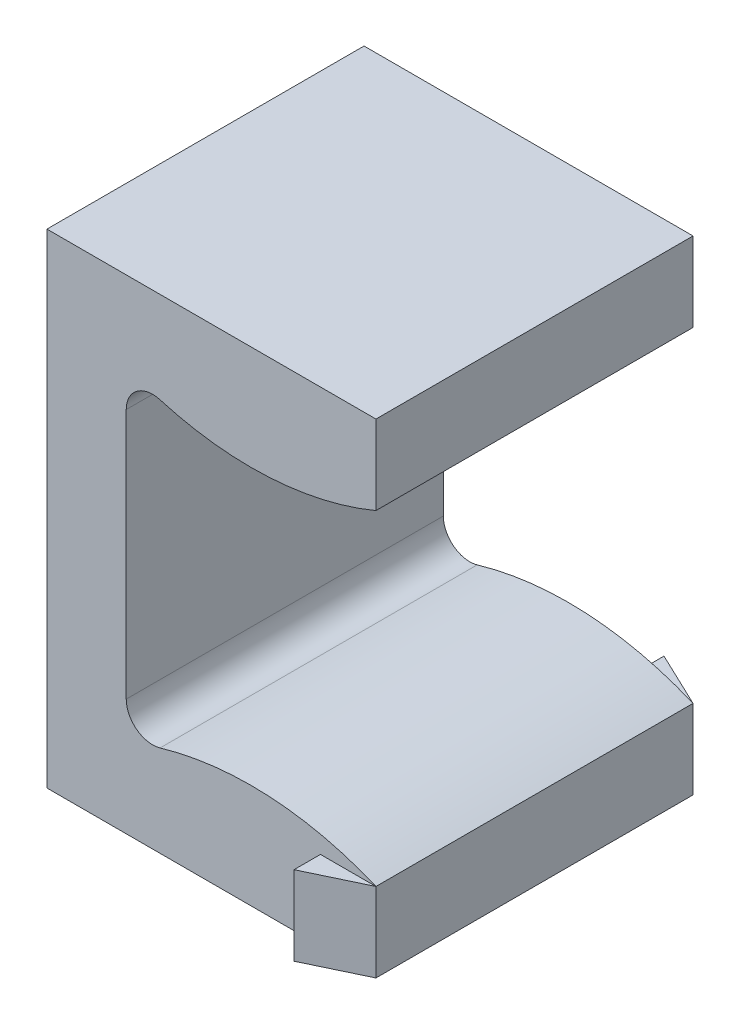
SolidWorks part; units mm, degrees
ref_plane "Front Plane" through (0, 0, 0) normal (0, 0, 1) x (1, 0, 0)
ref_plane "Top Plane" through (0, 0, 0) normal (0, 1, 0) x (1, 0, 0)
ref_plane "Right Plane" through (0, 0, 0) normal (1, 0, 0) x (0, 0, -1)
sketch "Sketch1" plane through (0, 0, 0) normal (0, 0, 1) x (1, 0, 0)
  line L2 (-159.7982, 9.1594) -> (-172.2482, 9.1594)
  line L3 (-172.2482, 9.1594) -> (-172.2482, -9.1594)
  line L7 (-169.2482, -22.8519) -> (-169.2482, 6.1594) construction
  line L13 (-142.8048, 5.1594) -> (-142.8048, -5.1594) construction
  line L23 (-159.7982, 6.1594) -> (-159.7982, 9.1594)
  line L28 (-164.5232, 5.2094) -> (-144.5007, 5.2094) construction
  line L30 (-169.2482, 6.1594) -> (-169.2482, 5.1594)
  line L34 (-169.2482, 5.1594) -> (-169.2482, -5.1594)
  line L35 (-172.2482, 0) -> (-169.2482, 0) construction
  line L36 (-169.2482, -6.1594) -> (-169.2482, -5.1594)
  line L37 (-159.7982, -6.1594) -> (-159.7982, -9.1594)
  line L38 (-159.7982, -9.1594) -> (-172.2482, -9.1594)
  arc A5 (-169.2482, 6.1594) -> (-159.7982, 6.1594) centre (-164.5232, 17.4347) ccw
  arc A6 (-169.2482, -6.1594) -> (-159.7982, -6.1594) centre (-164.5232, -17.4347) cw
  point P30 (-142.8048, 0)
  dimension "D6" = 12.2253
  dimension "D4" = 3
  dimension "D3" = 3
  dimension "D2" = 1
  dimension "D1" = 18.3188
  dimension "D5" = 12.45
extrude "MainBody" add sketch "Sketch1" along normal mid plane 12
sketch "Sketch3" plane through (0, -9.1594, 0) normal (0, -1, 0) x (1, 0, 0)
  line L0 (-159.7982, -6) -> (-161.8982, -7)
  line L1 (-161.8982, -7) -> (-161.8982, -6)
  line L2 (-172.2482, -6) -> (-159.7982, -6) construction
  line L3 (-161.8982, -6) -> (-159.7982, -6)
  line L5 (55, 0) -> (-55, 0) construction
  line L6 (-161.8982, 6) -> (-159.7982, 6)
  line L7 (-161.8982, 7) -> (-161.8982, 6)
  line L8 (-159.7982, 6) -> (-161.8982, 7)
  dimension "D1" = 2.1
  dimension "D2" = 1
extrude "Hook" add sketch "Sketch3" against normal up to vertex (3 mm away) up to point (-159.7982, -6.1594, -6)
fillet "Fillet2" radius 1 2 edges at (-169.2482, 6.1594, 0) (-169.2482, -6.1594, 0)
sketch "Sketch5" [suppressed] plane through (-172.2482, 0, 0) normal (-1, 0, 0) x (0, 0, 1)
  line L1 (-6, 9.1594) -> (6, 9.1594)
  line L2 (-6, 9.1594) -> (-6, -9.1594)
  line L3 (-6, -9.1594) -> (6, -9.1594)
  line L4 (6, 9.1594) -> (6, -9.1594)
extrude "Boss-Extrude1" [suppressed] add sketch "Sketch5" along normal blind 15
sketch "Sketch6" [suppressed] plane through (0, 9.1594, 0) normal (0, 1, 0) x (1, 0, 0)
  line L0 (-187.2482, -6) -> (-187.2482, 6) construction
  circle A0 centre (-182.2482, 0) radius 3.302
  dimension "D1" = 6.604
  dimension "D2" = 5
extrude "Cut-Extrude2" [suppressed] cut sketch "Sketch6" against normal through all
sketch "Sketch7" [suppressed] plane through (-172.2482, 0, 0) normal (-1, 0, 0) x (0, 0, 1)
  circle A0 centre (0, 0) radius 38.1
  dimension "D1" = 76.2
extrude "Boss-Extrude2" [suppressed] add sketch "Sketch7" along normal blind 5
fillet "Fillet3" [suppressed] radius 1
sketch "Sketch8" [suppressed] plane through (0, 0, 6) normal (0, 0, 1) x (1, 0, 0)
  line L6 (-172.2482, -0.635) -> (-173.4343, -0.635)
  line L8 (-172.2482, 0.635) -> (-173.4343, 0.635)
  line L10 (-172.2482, 0.635) -> (-173.4343, 0.635)
  line L11 (-172.2482, 0.635) -> (-172.2482, -0.635)
  line L12 (-159.7982, -9.1594) -> (-159.7982, -6.1594)
  line L13 (-159.7982, -9.1594) -> (-159.7982, -6.1594)
  line L14 (-169.2482, -6.1594) -> (-169.2482, 6.1594)
  line L15 (-159.7982, 6.1594) -> (-159.7982, 9.1594)
  line L16 (-159.7982, 9.1594) -> (-172.2482, 9.1594)
  line L17 (-172.2482, 9.1594) -> (-172.2482, -9.1594)
  line L18 (-172.2482, -9.1594) -> (-159.7982, -9.1594)
  line L21 (-169.2482, -6.1594) -> (-169.2482, 6.1594)
  line L22 (-159.7982, 6.1594) -> (-159.7982, 9.1594)
  line L23 (-159.7982, 9.1594) -> (-172.2482, 9.1594)
  line L24 (-172.2482, 9.1594) -> (-172.2482, -9.1594)
  line L25 (-172.2482, -9.1594) -> (-159.7982, -9.1594)
  line L26 (-172.2482, -0.635) -> (-173.4343, -0.635)
  arc A0 (-173.4343, 0.635) -> (-173.4343, -0.635) centre (-174.5342, 0) ccw
  arc A4 (-159.7982, -6.1594) -> (-169.2482, -6.1594) centre (-164.5232, -17.4347) ccw
  arc A7 (-169.2482, 6.1594) -> (-159.7982, 6.1594) centre (-164.5232, 17.4347) ccw
  arc A8 (-159.7982, -6.1594) -> (-169.2482, -6.1594) centre (-164.5232, -17.4347) ccw
  arc A11 (-169.2482, 6.1594) -> (-159.7982, 6.1594) centre (-164.5232, 17.4347) ccw
  point P6 (-172.2482, 0)
  line M14 (-172.2482, 9.1594) -> (-172.2482, -9.1594)
  dimension "D2" = 1.27
  dimension "D1" = 0
  dimension "D3" = 2.286
extrude "Slot" [suppressed] add sketch "Sketch8" against normal up to surface (12 mm away) contours L8 A0 L6 M14 up to face at (-165.6835, -0.5599, -6)
sketch "Sketch10" [suppressed] plane through (0, 0, -6) normal (0, 0, -1) x (-1, 0, 0)
  line L0 (166.0232, -9.1594) -> (172.2482, -9.1594)
  line L3 (172.2482, -9.1594) -> (166.0232, -9.1594)
  line L5 (172.2482, -9.1594) -> (187.9767, -44.4861)
  line L6 (195.4932, -61.3685) -> (192.3182, -61.3685)
  line L7 (159.7982, -6.1594) -> (159.7982, -9.1594)
  line L8 (159.7982, -6.1594) -> (159.7982, -9.1594)
  line L9 (159.7982, -9.1594) -> (172.2482, -9.1594)
  line L10 (172.2482, -9.1594) -> (172.2482, 9.1594)
  line L11 (172.2482, 9.1594) -> (159.7982, 9.1594)
  line L12 (159.7982, 9.1594) -> (159.7982, 6.1594)
  line L13 (169.2482, 6.1594) -> (169.2482, -6.1594)
  line L16 (159.7982, -9.1594) -> (172.2482, -9.1594)
  line L17 (172.2482, -9.1594) -> (172.2482, 9.1594)
  line L18 (172.2482, 9.1594) -> (159.7982, 9.1594)
  line L19 (159.7982, 9.1594) -> (159.7982, 6.1594)
  line L20 (169.2482, 6.1594) -> (169.2482, -6.1594)
  line L21 (195.4932, -61.3685) -> (201.8432, -61.3685)
  line L22 (201.8432, -61.3685) -> (201.8432, -59.781)
  line L24 (192.666, -55.0185) -> (200.9772, -55.0185)
  line L25 (169.0732, -9.1594) -> (192.3182, -61.3685)
  line L28 (201.8432, -59.781) -> (194.7864, -59.781)
  line L31 (193.3728, -56.606) -> (200.9772, -56.606)
  line L42 (200.9772, -55.0185) -> (200.9772, -56.606)
  line L43 (187.9767, -44.4861) -> (195.4932, -61.3685)
  arc A4 (169.2482, -6.1594) -> (159.7982, -6.1594) centre (164.5232, -17.4347) ccw
  arc A5 (159.7982, 6.1594) -> (169.2482, 6.1594) centre (164.5232, 17.4347) ccw
  arc A8 (169.2482, -6.1594) -> (159.7982, -6.1594) centre (164.5232, -17.4347) ccw
  arc A9 (159.7982, 6.1594) -> (169.2482, 6.1594) centre (164.5232, 17.4347) ccw
  dimension "D5" = 6.35
  dimension "D7" = 3.175
  dimension "D8" = 3.175
  dimension "D2" = 57.15
  dimension "D10" = 1.5875
  dimension "D13" = 114
  dimension "D14" = 114
  dimension "D3" = 1.5875
  dimension "D4" = 3.175
extrude "Boss-Extrude3" [suppressed] add sketch "Sketch10" against normal up to surface (12 mm away) up to face at (-165.6835, -0.5599, 6)
sketch "Sketch11" [suppressed] plane through (0, 0, -6) normal (0, 0, -1) x (-1, 0, 0)
  line L0 (159.7982, -9.1594) -> (159.7982, 9.1594)
  line L11 (169.2482, 6.1594) -> (169.2482, -6.1594)
  line L12 (159.7982, -6.1594) -> (159.7982, -9.1594)
  line L13 (159.7982, -9.1594) -> (169.0732, -9.1594)
  line L14 (169.0732, -9.1594) -> (192.3182, -61.3685)
  line L15 (192.3182, -61.3685) -> (201.8432, -61.3685)
  line L16 (201.8432, -61.3685) -> (201.8432, -59.781)
  line L17 (201.8432, -59.781) -> (194.7864, -59.781)
  line L18 (194.7864, -59.781) -> (193.3728, -56.606)
  line L19 (172.2482, -9.1594) -> (172.2482, 9.1594)
  line L20 (172.2482, 9.1594) -> (159.7982, 9.1594)
  line L21 (159.7982, 9.1594) -> (159.7982, 6.1594)
  line L22 (169.2482, 6.1594) -> (169.2482, -6.1594)
  line L23 (159.7982, -6.1594) -> (159.7982, -9.1594)
  line L24 (159.7982, -9.1594) -> (169.0732, -9.1594)
  line L25 (169.0732, -9.1594) -> (192.3182, -61.3685)
  line L26 (192.3182, -61.3685) -> (201.8432, -61.3685)
  line L27 (201.8432, -61.3685) -> (201.8432, -59.781)
  line L28 (201.8432, -59.781) -> (194.7864, -59.781)
  line L29 (194.7864, -59.781) -> (193.3728, -56.606)
  line L30 (172.2482, -9.1594) -> (172.2482, 9.1594)
  line L31 (172.2482, 9.1594) -> (159.7982, 9.1594)
  line L32 (159.7982, 9.1594) -> (159.7982, 6.1594)
  line L37 (193.3728, -56.606) -> (200.9772, -56.606)
  line L38 (193.3728, -56.606) -> (200.9772, -56.606)
  line L39 (200.9772, -56.606) -> (200.9772, -55.0185)
  line L40 (200.9772, -56.606) -> (200.9772, -55.0185)
  line L41 (192.666, -55.0185) -> (172.2482, -9.1594)
  line L42 (192.666, -55.0185) -> (172.2482, -9.1594)
  line L44 (200.9772, -55.0185) -> (192.666, -55.0185)
  line L45 (200.9772, -55.0185) -> (192.666, -55.0185)
  arc A2 (159.7982, 6.1594) -> (169.2482, 6.1594) centre (164.5232, 17.4347) ccw
  arc A3 (169.2482, -6.1594) -> (159.7982, -6.1594) centre (164.5232, -17.4347) ccw
  arc A4 (159.7982, 6.1594) -> (169.2482, 6.1594) centre (164.5232, 17.4347) ccw
  arc A5 (169.2482, -6.1594) -> (159.7982, -6.1594) centre (164.5232, -17.4347) ccw
  arc M14 (159.7982, 6.1594) -> (169.2482, 6.1594) centre (164.5232, 17.4347) ccw
  line M15 (169.2482, 6.1594) -> (169.2482, -6.1594)
  arc M16 (169.2482, -6.1594) -> (159.7982, -6.1594) centre (164.5232, -17.4347) ccw
  dimension "D1" = 0
extrude "Boss-Extrude4" [suppressed] add sketch "Sketch11" against normal up to surface (12 mm away) contours L0 M16 M15 M14 up to face at (-165.6835, -0.5599, 6)
sketch "Sketch12" [suppressed] plane through (0, 0, -6) normal (0, 0, -1) x (-1, 0, 0)
  line L0 (159.7982, -9.1594) -> (159.7982, -5.9844)
  line L1 (159.7982, -5.9844) -> (162.0842, -5.9844)
  line L3 (162.0842, -5.2351) -> (159.7982, -5.2351)
  line L4 (162.0842, -5.2351) -> (162.0842, -6.7337)
  line L5 (162.0842, -6.7337) -> (159.7982, -6.7337)
  line L6 (159.7982, -5.2351) -> (159.7982, -6.7337)
  line L7 (162.0842, -5.2351) -> (159.7982, -6.7337) construction
  line L8 (162.0842, -6.7337) -> (159.7982, -5.2351) construction
  line L9 (172.2482, 9.1594) -> (159.7982, 9.1594)
  line L10 (159.7982, 9.1594) -> (159.7982, -9.1594)
  line L11 (159.7982, -9.1594) -> (169.0732, -9.1594)
  line L12 (169.0732, -9.1594) -> (192.3182, -61.3685)
  line L13 (192.3182, -61.3685) -> (201.8432, -61.3685)
  line L14 (201.8432, -61.3685) -> (201.8432, -59.781)
  line L15 (201.8432, -59.781) -> (194.7864, -59.781)
  line L16 (194.7864, -59.781) -> (193.3728, -56.606)
  line L17 (172.2482, -9.1594) -> (172.2482, 9.1594)
  line L18 (172.2482, 9.1594) -> (159.7982, 9.1594)
  line L19 (159.7982, 9.1594) -> (159.7982, -9.1594)
  line L20 (159.7982, -9.1594) -> (169.0732, -9.1594)
  line L21 (169.0732, -9.1594) -> (192.3182, -61.3685)
  line L22 (192.3182, -61.3685) -> (201.8432, -61.3685)
  line L23 (201.8432, -61.3685) -> (201.8432, -59.781)
  line L24 (201.8432, -59.781) -> (194.7864, -59.781)
  line L25 (194.7864, -59.781) -> (193.3728, -56.606)
  line L26 (172.2482, -9.1594) -> (172.2482, 9.1594)
  line L38 (193.3728, -56.606) -> (200.9772, -56.606)
  line L39 (193.3728, -56.606) -> (200.9772, -56.606)
  line L40 (200.9772, -56.606) -> (200.9772, -55.0185)
  line L42 (192.666, -55.0185) -> (172.2482, -9.1594)
  line L43 (192.666, -55.0185) -> (172.2482, -9.1594)
  line L45 (200.9772, -56.606) -> (200.9772, -55.0185)
  line L46 (200.9772, -55.0185) -> (192.666, -55.0185)
  line L47 (200.9772, -55.0185) -> (192.666, -55.0185)
  circle A0 centre (162.0842, -5.9844) radius 1.3843
  point P8 (160.9412, -5.9844)
  line M13 (159.7982, 9.1594) -> (159.7982, -9.1594)
  dimension "D4" = 2.7686
  dimension "D2" = 3.175
  dimension "D3" = 2.286
  dimension "D5" = 1.4986
extrude "Cut-Extrude3" [suppressed] cut sketch "Sketch12" against normal up to surface (12 mm away) contours L5 A0 L3 L4 | L1 A0 L5 L4 | A0 L1 L5 M13 | L3 A0 L1 L4 | A0 L3 L1 M13 up to face at (-165.6835, -0.5599, 6)
pattern_linear "LPattern1" [suppressed] count 4 spacing 4.28 of bodies 117
sketch "Sketch15" [suppressed] plane through (0, 0, 6) normal (0, 0, 1) x (1, 0, 0)
  line L1 (-172.2482, -9.1594) -> (-179.8682, -9.1594)
  line L2 (-172.2482, -9.1594) -> (-172.2482, 47.9906)
  line L3 (-172.2482, 47.9906) -> (-179.8682, 47.9906)
  line L4 (-179.8682, -9.1594) -> (-179.8682, 47.9906)
  dimension "D1" = 7.62
  dimension "D2" = 57.15
extrude "Boss-Extrude6" [suppressed] add sketch "Sketch15" against normal up to surface (12 mm away) up to face at (-165.6835, -0.5599, -6)
sketch "Sketch16" [suppressed] plane through (0, 0, 6) normal (0, 0, 1) x (1, 0, 0)
  line L0 (-172.2482, 9.1594) -> (-172.2482, 47.9906) construction
  line L1 (-172.2482, 44.8156) -> (-174.5342, 44.8156)
  line L2 (-172.2482, 44.8156) -> (-172.2482, 43.2916)
  line L3 (-172.2482, 43.2916) -> (-174.5342, 43.2916)
  line L4 (-174.5342, 44.8156) -> (-174.5342, 43.2916)
  line L5 (-172.2482, 47.9906) -> (-179.8682, 47.9906) construction
  circle A0 centre (-174.5342, 44.0536) radius 1.4605
  line M12 (-172.2482, 9.1594) -> (-172.2482, 47.9906)
  dimension "D4" = 2.921
  dimension "D1" = 3.175
  dimension "D2" = 1.524
  dimension "D3" = 2.286
extrude "Cut-Extrude6" [suppressed] cut sketch "Sketch16" against normal up to surface (12 mm away) contours A0 L3 L1 M12 | L3 A0 L1 L4 | L1 A0 L3 L4 up to face at (-165.6835, -0.5599, -6)
pattern_linear "LPattern3" [suppressed] count 7 spacing 5.08 of bodies 124
fillet "Fillet5" [suppressed] radius 2.54
equation "\"HookThickness\"= 3mm"
equation "\"D3@Sketch1\"=\"HookThickness\""
equation "\"D4@Sketch1\"=\"HookThickness\""
equation "\"CylinderDiameter\"=3"
equation "\"D1@Sketch7\"=\"CylinderDiameter\""
equation "\"Mount Tolerance\"= .005in"
equation "\"Mount Thickness\"= .0625in"
equation "\"Mount Angle\"= 114"
equation "\"D14@Sketch10\"=\"Mount Angle\""
equation "\"D13@Sketch10\"= \"Mount Angle\""
equation "\"Joint Radius\"= .05in"
equation "\"Joint Thickness\"= .05in"
equation "\"Joint Tolerance\"= .009in"
equation "\"D4@Sketch12\"= (\"Joint Radius\" * 2) + \"Joint Tolerance\""
equation "\"D5@Sketch12\"= \"Joint Thickness\" + \"Joint Tolerance\""
